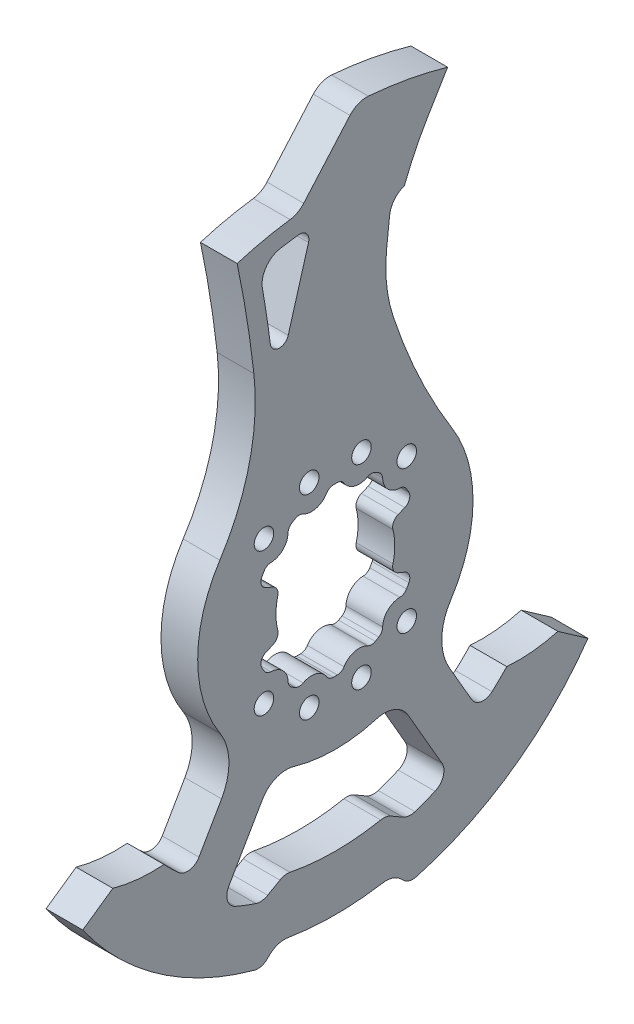
SolidWorks part; units mm, degrees
material "AR500"
ref_plane "Front Plane" through (0, 0, 0) normal (0, 0, 1) x (1, 0, 0)
ref_plane "Top Plane" through (0, 0, 0) normal (0, 1, 0) x (1, 0, 0)
ref_plane "Right Plane" through (0, 0, 0) normal (1, 0, 0) x (0, 0, -1)
other "Center of Mass"
sketch "Sketch1" plane through (0, 0, 0) normal (1, 0, 0) x (0, 0, -1)
  circle A0 centre (0, 0) radius 139.7 construction
  circle A1 centre (0, 0) radius 106.68 construction
  circle A2 centre (0, 0) radius 44.45 construction
  dimension "D1" = 279.4
  dimension "D2" = 33.02
  dimension "D3" = 88.9
sketch "Sketch2" plane through (0, 0, 0) normal (1, 0, 0) x (0, 0, -1)
  line L0 (0, 0) -> (38.858, 134.187) construction
  line L1 (38.858, 134.187) -> (32.2885, 123.3181)
  line L2 (0, 0) -> (0, 61.679) construction
  line L3 (7.5549, 139.4956) -> (-12.8644, 116.1296)
  line L4 (-33.9764, 111.7908) -> (-39.3372, 137.2171) construction
  line L5 (23.88, 106.192) -> (16.7676, 87.8077) construction
  line L6 (23.88, 106.192) -> (19.2337, 104.1379)
  line L7 (19.2337, 104.1379) -> (17.7417, 90.2907)
  line L8 (-33.9764, 111.7908) -> (-3.6464, 121.009) construction
  line L10 (0, -100.33) -> (0, 0) construction
  line L11 (-20.0866, -98.2987) -> (-25.4, -103.6121)
  line L16 (-49.9001, -64.1593) -> (-32.7957, -34.5337)
  line L17 (87.3871, -61.1891) -> (76.9839, -53.9047)
  line L18 (-87.3871, -61.1891) -> (-76.9839, -53.9047)
  line L19 (49.9001, -64.1593) -> (32.7957, -34.5337)
  line L24 (53.8815, -53.8815) -> (0, 0) construction
  line L25 (20.0866, -98.2987) -> (25.4, -103.6121)
  circle A0 centre (0, 0) radius 139.7 construction
  arc A1 (38.858, 134.187) -> (7.5549, 139.4956) centre (0, 0) ccw
  arc A2 (-12.8644, 116.1296) -> (-33.9764, 111.7908) centre (0, 0) ccw
  arc A3 (32.2885, 123.3181) -> (23.88, 106.192) centre (125.9607, 66.6999) ccw
  arc A4 (40.4523, 25.1346) -> (32.7957, -34.5337) centre (0, 0) cw
  circle A5 centre (0, 0) radius 44.45 construction
  arc A6 (19.9828, 69.006) -> (17.7417, 90.2907) centre (68.2493, 84.8485) cw
  arc A7 (-33.9764, 111.7908) -> (-28.182, 75.8993) centre (-406.7808, 33.191) cw
  arc A8 (-28.182, 75.8993) -> (-39.9622, 25.9068) centre (-103.9018, 67.3576) cw
  arc A9 (-39.9622, 25.9068) -> (-32.7957, -34.5337) centre (0, 0) ccw
  arc A10 (-87.3871, -61.1891) -> (-25.4, -103.6121) centre (0, 0) ccw
  circle A11 centre (0, 0) radius 106.68 construction
  arc A18 (-76.9839, -53.9047) -> (-59.2852, -55.6031) centre (-63.357, -4.9665) ccw
  arc A19 (-59.2852, -55.6031) -> (-49.9001, -64.1593) centre (0, 0) ccw
  arc A20 (-20.0866, -98.2987) -> (20.0866, -98.2987) centre (0, 0) ccw
  arc A21 (59.2852, -55.6031) -> (49.9001, -64.1593) centre (0, 0) cw
  arc A22 (76.9839, -53.9047) -> (59.2852, -55.6031) centre (63.357, -4.9665) cw
  arc A23 (87.3871, -61.1891) -> (25.4, -103.6121) centre (0, 0) cw
  arc A25 (19.9828, 69.006) -> (40.4523, 25.1346) centre (213.0489, 132.3758) ccw
  dimension "D4" = 22.86
  dimension "D11" = 95.25
  dimension "D13" = 50.8
  dimension "D14" = 381
  dimension "D16" = 76.2
  dimension "D19" = 6.35
  dimension "D21" = 55
  dimension "D26" = 17.78
  dimension "D22" = 25.4
  dimension "D23" = 50.8
  dimension "D27" = 12.7
  dimension "D29" = 203.2
  dimension "D1" = 15
  dimension "D2" = 16.15
  dimension "D3" = 10
  dimension "D5" = 31.75
  dimension "D6" = 12.7
  dimension "D7" = 31.75
  dimension "D8" = 5
  dimension "D9" = 45
  dimension "D10" = 10
  dimension "D12" = 5.08
  dimension "D15" = 85
  dimension "D17" = 76.2
  dimension "D18" = 25.4
  dimension "D20" = 45
  dimension "D24" = 12.7
  dimension "D25" = 45
  dimension "D28" = 30
extrude "Boss-Extrude1" add sketch "Sketch2" along normal mid plane 12.7
sketch "Sketch3" plane through (6.35, 0, 0) normal (1, 0, 0) x (0, 0, -1)
  line L1 (-9.2851, 105.7206) -> (-16.3113, 81.4575)
  line L2 (17.7417, 90.2907) -> (19.2337, 104.1379) construction
  line L3 (-3.258, 62.2657) -> (5.5274, 106.8394) construction
  line L4 (19.2337, 104.1379) -> (-8.1789, 109.5409) construction
  arc A0 (-12.8644, 116.1296) -> (-33.9764, 111.7908) centre (0, 0) ccw construction
  arc A1 (-28.182, 75.8993) -> (-33.9764, 111.7908) centre (-406.7808, 33.191) ccw construction
  arc A2 (-9.2851, 105.7206) -> (-12.6998, 109.7577) centre (-12.3348, 106.6038) ccw
  arc A3 (-12.8644, 116.1296) -> (-33.9764, 111.7908) centre (0, 0) ccw construction
  arc A4 (-28.182, 75.8993) -> (-33.9764, 111.7908) centre (-406.7808, 33.191) ccw construction
  arc A5 (-12.6998, 109.7577) -> (-26.5758, 107.2463) centre (0, 0) ccw
  arc A6 (-22.5107, 81.941) -> (-26.5758, 107.2463) centre (-406.7808, 33.191) ccw
  arc A7 (-21.8721, 76.6111) -> (-26.5758, 107.2463) centre (-406.7808, 33.191) ccw construction
  arc A8 (-12.1653, 109.8182) -> (-26.5758, 107.2463) centre (0, 0) ccw construction
  arc A14 (-22.5107, 81.941) -> (-16.3113, 81.4575) centre (-19.361, 82.3406) ccw
  point P18 (19.2337, 104.1379)
  dimension "D5" = 3.175
  dimension "D7" = 3.175
  dimension "D3" = 10
  dimension "D4" = 27.94
  dimension "D1" = 6.35
extrude "Cut-Extrude1" cut sketch "Sketch3" against normal through all
fillet "Fillet1" radius 7.62 6 edges at (0, 104.1379, -19.2337) (0, 107.2463, 26.5758) (0, 139.4956, -7.5549) (0, 116.1296, 12.8644) (0, -98.2987, -20.0866) (0, -98.2987, 20.0866)
fillet "Fillet4" radius 19.05 2 edges at (0, -34.5337, -32.7957) (0, -34.5337, 32.7957)
fillet "Fillet2" radius 4.572 4 edges at (0, -103.6121, 25.4) (0, -103.6121, -25.4) (0, -64.1593, -49.9001) (0, -64.1593, 49.9001)
sketch "Sketch4" plane through (6.35, 0, 0) normal (1, 0, 0) x (0, 0, -1)
  line L0 (-21.1843, -46.1721) -> (-39.646, -78.1487)
  line L1 (-39.3687, -45.9185) -> (-47.1846, -59.4559) construction
  line L2 (0, -81.28) -> (0, -50.8)
  line L3 (-25.3274, -83.8901) -> (-17.5035, -79.373)
  line L4 (-11.6185, -94.3061) -> (-25.8749, -102.5371) construction
  arc A0 (-39.646, -78.1487) -> (-25.3274, -83.8901) centre (0, 0) ccw
  arc A1 (0, -50.8) -> (-21.1843, -46.1721) centre (0, 0) cw
  circle A2 centre (0, 0) radius 44.45 construction
  circle A3 centre (0, 0) radius 106.68 construction
  arc A4 (-17.5035, -79.373) -> (0, -81.28) centre (0, 0) ccw
  arc A5 (-16.2916, -98.9984) -> (16.2916, -98.9984) centre (0, 0) ccw construction
  arc A6 (-87.3871, -61.1891) -> (-27.9851, -102.9439) centre (0, 0) ccw construction
  arc A7 (-16.2916, -98.9984) -> (-22.9171, -101.1292) centre (-17.5289, -106.5173) ccw construction
  dimension "D1" = 50.8
  dimension "D3" = 19.05
  dimension "D4" = 19.05
  dimension "D2" = 15.875
  dimension "D5" = 30
  dimension "D6" = 15.875
extrude "Cut-Extrude2" cut sketch "Sketch4" against normal through all
mirror "Mirror1" about plane through (-6.35, -81.28, 0) normal (0, 0, -1) of "Cut-Extrude2"
fillet "Fillet3" radius 5.08 6 edges at (0, -78.1487, -39.646) (0, -83.8901, -25.3274) (0, -79.373, -17.5035) (0, -79.373, 17.5035) (0, -83.8901, 25.3274) (0, -78.1487, 39.646)
fillet "Fillet5" radius 9.525 2 edges at (0, -46.1721, -21.1843) (0, -46.1721, 21.1843)
ref_axis "Axis2" through (-6.985, 0, 0) along (1, 0, 0)
sketch "Sketch5" plane through (-6.35, 0, 0) normal (-1, 0, 0) x (0, 0, 1)
  line L8 (21.7068, 8.7163) -> (24.0357, 9.681)
  line L9 (24.0357, -9.681) -> (21.7068, -8.7163)
  line L10 (-21.7068, -8.7163) -> (-24.0357, -9.681)
  line L11 (-24.0357, 9.681) -> (-21.7068, 8.7163)
  line L12 (21.7068, 8.7163) -> (24.0357, 9.681)
  line L13 (24.0357, -9.681) -> (21.7068, -8.7163)
  line L14 (-21.7068, -8.7163) -> (-24.0357, -9.681)
  line L15 (-24.0357, 9.681) -> (-21.7068, 8.7163)
  arc A104 (13.8013, 25.3108) -> (11.1292, 25.3125) centre (12.4637, 22.8578) ccw
  arc A105 (15.0192, 24.6076) -> (13.8013, 25.3108) centre (0, 0) ccw
  arc A106 (16.3566, 22.2944) -> (15.0192, 24.6076) centre (13.5636, 22.2228) ccw
  arc A107 (16.3566, 22.2944) -> (22.2944, 16.3566) centre (22.4506, 22.4506) ccw
  arc A108 (24.6076, 15.0192) -> (22.2944, 16.3566) centre (22.2228, 13.5636) ccw
  arc A109 (25.4311, 13.5782) -> (24.6076, 15.0192) centre (0, 0) ccw
  arc A110 (24.0357, 9.681) -> (25.4311, 13.5782) centre (22.9664, 12.2623) ccw
  arc A111 (21.7068, 8.7163) -> (19.9218, 5.139) centre (22.8732, 5.9003) ccw
  arc A112 (19.9218, -5.139) -> (19.9218, 5.139) centre (0, 0) ccw
  arc A113 (19.9218, -5.139) -> (21.7068, -8.7163) centre (22.8732, -5.9003) ccw
  arc A114 (25.4311, -13.5782) -> (24.0357, -9.681) centre (22.9664, -12.2623) ccw
  arc A115 (24.6076, -15.0192) -> (25.4311, -13.5782) centre (0, 0) ccw
  arc A116 (22.2944, -16.3566) -> (24.6076, -15.0192) centre (22.2228, -13.5636) ccw
  arc A117 (22.2944, -16.3566) -> (16.3566, -22.2944) centre (22.4506, -22.4506) ccw
  arc A118 (15.0192, -24.6076) -> (16.3566, -22.2944) centre (13.5636, -22.2228) ccw
  arc A119 (13.8013, -25.3108) -> (15.0192, -24.6076) centre (0, 0) ccw
  arc A120 (11.1292, -25.3125) -> (13.8013, -25.3108) centre (12.4637, -22.8578) ccw
  arc A121 (11.1292, -25.3125) -> (3.0181, -27.4858) centre (8.2175, -30.6681) ccw
  arc A122 (0.7032, -28.8204) -> (3.0181, -27.4858) centre (0.635, -26.0273) ccw
  arc A123 (-0.7032, -28.8204) -> (0.7032, -28.8204) centre (0, 0) ccw
  arc A124 (-3.0181, -27.4858) -> (-0.7032, -28.8204) centre (-0.635, -26.0273) ccw
  arc A125 (-3.0181, -27.4858) -> (-11.1292, -25.3125) centre (-8.2175, -30.6681) ccw
  arc A126 (-13.8013, -25.3108) -> (-11.1292, -25.3125) centre (-12.4637, -22.8578) ccw
  arc A127 (-15.0192, -24.6076) -> (-13.8013, -25.3108) centre (0, 0) ccw
  arc A128 (-16.3566, -22.2944) -> (-15.0192, -24.6076) centre (-13.5636, -22.2228) ccw
  arc A129 (-16.3566, -22.2944) -> (-22.2944, -16.3566) centre (-22.4506, -22.4506) ccw
  arc A130 (-24.6076, -15.0192) -> (-22.2944, -16.3566) centre (-22.2228, -13.5636) ccw
  arc A131 (-25.4311, -13.5782) -> (-24.6076, -15.0192) centre (0, 0) ccw
  arc A132 (-24.0357, -9.681) -> (-25.4311, -13.5782) centre (-22.9664, -12.2623) ccw
  arc A133 (-21.7068, -8.7163) -> (-19.9218, -5.139) centre (-22.8732, -5.9003) ccw
  arc A134 (-19.9218, 5.139) -> (-19.9218, -5.139) centre (0, 0) ccw
  arc A135 (-19.9218, 5.139) -> (-21.7068, 8.7163) centre (-22.8732, 5.9003) ccw
  arc A136 (-25.4311, 13.5782) -> (-24.0357, 9.681) centre (-22.9664, 12.2623) ccw
  arc A137 (-24.6076, 15.0192) -> (-25.4311, 13.5782) centre (0, 0) ccw
  arc A138 (-22.2944, 16.3566) -> (-24.6076, 15.0192) centre (-22.2228, 13.5636) ccw
  arc A139 (-22.2944, 16.3566) -> (-16.3566, 22.2944) centre (-22.4506, 22.4506) ccw
  arc A140 (-15.0192, 24.6076) -> (-16.3566, 22.2944) centre (-13.5636, 22.2228) ccw
  arc A141 (-13.8013, 25.3108) -> (-15.0192, 24.6076) centre (0, 0) ccw
  arc A142 (-11.1292, 25.3125) -> (-13.8013, 25.3108) centre (-12.4637, 22.8578) ccw
  arc A143 (-11.1292, 25.3125) -> (-3.0181, 27.4858) centre (-8.2175, 30.6681) ccw
  arc A144 (-0.7032, 28.8204) -> (-3.0181, 27.4858) centre (-0.635, 26.0273) ccw
  arc A145 (0.7032, 28.8204) -> (-0.7032, 28.8204) centre (0, 0) ccw
  arc A146 (3.0181, 27.4858) -> (0.7032, 28.8204) centre (0.635, 26.0273) ccw
  arc A147 (3.0181, 27.4858) -> (11.1292, 25.3125) centre (8.2175, 30.6681) ccw
  arc A148 (13.8013, 25.3108) -> (11.1292, 25.3125) centre (12.4637, 22.8578) ccw
  arc A149 (15.0192, 24.6076) -> (13.8013, 25.3108) centre (0, 0) ccw
  arc A150 (16.3566, 22.2944) -> (15.0192, 24.6076) centre (13.5636, 22.2228) ccw
  arc A151 (16.3566, 22.2944) -> (22.2944, 16.3566) centre (22.4506, 22.4506) ccw
  arc A152 (24.6076, 15.0192) -> (22.2944, 16.3566) centre (22.2228, 13.5636) ccw
  arc A153 (25.4311, 13.5782) -> (24.6076, 15.0192) centre (0, 0) ccw
  arc A154 (24.0357, 9.681) -> (25.4311, 13.5782) centre (22.9664, 12.2623) ccw
  arc A155 (21.7068, 8.7163) -> (19.9218, 5.139) centre (22.8732, 5.9003) ccw
  arc A156 (19.9218, -5.139) -> (19.9218, 5.139) centre (0, 0) ccw
  arc A157 (19.9218, -5.139) -> (21.7068, -8.7163) centre (22.8732, -5.9003) ccw
  arc A158 (25.4311, -13.5782) -> (24.0357, -9.681) centre (22.9664, -12.2623) ccw
  arc A159 (24.6076, -15.0192) -> (25.4311, -13.5782) centre (0, 0) ccw
  arc A160 (22.2944, -16.3566) -> (24.6076, -15.0192) centre (22.2228, -13.5636) ccw
  arc A161 (22.2944, -16.3566) -> (16.3566, -22.2944) centre (22.4506, -22.4506) ccw
  arc A162 (15.0192, -24.6076) -> (16.3566, -22.2944) centre (13.5636, -22.2228) ccw
  arc A163 (13.8013, -25.3108) -> (15.0192, -24.6076) centre (0, 0) ccw
  arc A164 (11.1292, -25.3125) -> (13.8013, -25.3108) centre (12.4637, -22.8578) ccw
  arc A165 (11.1292, -25.3125) -> (3.0181, -27.4858) centre (8.2175, -30.6681) ccw
  arc A166 (0.7032, -28.8204) -> (3.0181, -27.4858) centre (0.635, -26.0273) ccw
  arc A167 (-0.7032, -28.8204) -> (0.7032, -28.8204) centre (0, 0) ccw
  arc A168 (-3.0181, -27.4858) -> (-0.7032, -28.8204) centre (-0.635, -26.0273) ccw
  arc A169 (-3.0181, -27.4858) -> (-11.1292, -25.3125) centre (-8.2175, -30.6681) ccw
  arc A170 (-13.8013, -25.3108) -> (-11.1292, -25.3125) centre (-12.4637, -22.8578) ccw
  arc A171 (-15.0192, -24.6076) -> (-13.8013, -25.3108) centre (0, 0) ccw
  arc A172 (-16.3566, -22.2944) -> (-15.0192, -24.6076) centre (-13.5636, -22.2228) ccw
  arc A173 (-16.3566, -22.2944) -> (-22.2944, -16.3566) centre (-22.4506, -22.4506) ccw
  arc A174 (-24.6076, -15.0192) -> (-22.2944, -16.3566) centre (-22.2228, -13.5636) ccw
  arc A175 (-25.4311, -13.5782) -> (-24.6076, -15.0192) centre (0, 0) ccw
  arc A176 (-24.0357, -9.681) -> (-25.4311, -13.5782) centre (-22.9664, -12.2623) ccw
  arc A177 (-21.7068, -8.7163) -> (-19.9218, -5.139) centre (-22.8732, -5.9003) ccw
  arc A178 (-19.9218, 5.139) -> (-19.9218, -5.139) centre (0, 0) ccw
  arc A179 (-19.9218, 5.139) -> (-21.7068, 8.7163) centre (-22.8732, 5.9003) ccw
  arc A180 (-25.4311, 13.5782) -> (-24.0357, 9.681) centre (-22.9664, 12.2623) ccw
  arc A181 (-24.6076, 15.0192) -> (-25.4311, 13.5782) centre (0, 0) ccw
  arc A182 (-22.2944, 16.3566) -> (-24.6076, 15.0192) centre (-22.2228, 13.5636) ccw
  arc A183 (-22.2944, 16.3566) -> (-16.3566, 22.2944) centre (-22.4506, 22.4506) ccw
  arc A184 (-15.0192, 24.6076) -> (-16.3566, 22.2944) centre (-13.5636, 22.2228) ccw
  arc A185 (-13.8013, 25.3108) -> (-15.0192, 24.6076) centre (0, 0) ccw
  arc A186 (-11.1292, 25.3125) -> (-13.8013, 25.3108) centre (-12.4637, 22.8578) ccw
  arc A187 (-11.1292, 25.3125) -> (-3.0181, 27.4858) centre (-8.2175, 30.6681) ccw
  arc A188 (-0.7032, 28.8204) -> (-3.0181, 27.4858) centre (-0.635, 26.0273) ccw
  arc A189 (0.7032, 28.8204) -> (-0.7032, 28.8204) centre (0, 0) ccw
  arc A190 (3.0181, 27.4858) -> (0.7032, 28.8204) centre (0.635, 26.0273) ccw
  arc A191 (3.0181, 27.4858) -> (11.1292, 25.3125) centre (8.2175, 30.6681) ccw
  point P144 (0, 0)
  point P145 (0, 0)
  dimension "D1" = 0.254
extrude "Cut-Extrude4" cut sketch "Sketch5" against normal through all
hole_wizard "1/4 Clearance Hole1" positions "Sketch6" profile "Sketch8" hole size "1/4" standard "ANSI Inch" end condition through all
sketch "Sketch6" plane through (6.35, 0, 0) normal (1, 0, 0) x (0, 0, -1)
  point P0 (9.0393, 33.735)
  point P3 (9.0393, 33.735)
sketch "Sketch8" plane through (6.35, 33.735, -9.0393) normal (0, 1, 0) x (0, 0, -1)
  line L0 (0, 0) -> (0, 12.7)
  line L1 (0, 12.7) -> (3.3782, 12.7)
  line L2 (3.3782, 12.7) -> (3.3782, 0)
  line L5 (3.3782, 0) -> (0, 0)
  line L11 (0, -6.35) -> (0, 107.95) construction
  dimension "Thru Hole Dia." = 6.7564
  dimension "Thru Hole Depth" = 12.7
pattern_circular "CirPattern1" count 12 over 360 about axis through (-6.985, 0, 0) along (1, 0, 0) skipping 3, 4, 9, 10 of "1/4 Clearance Hole1"
